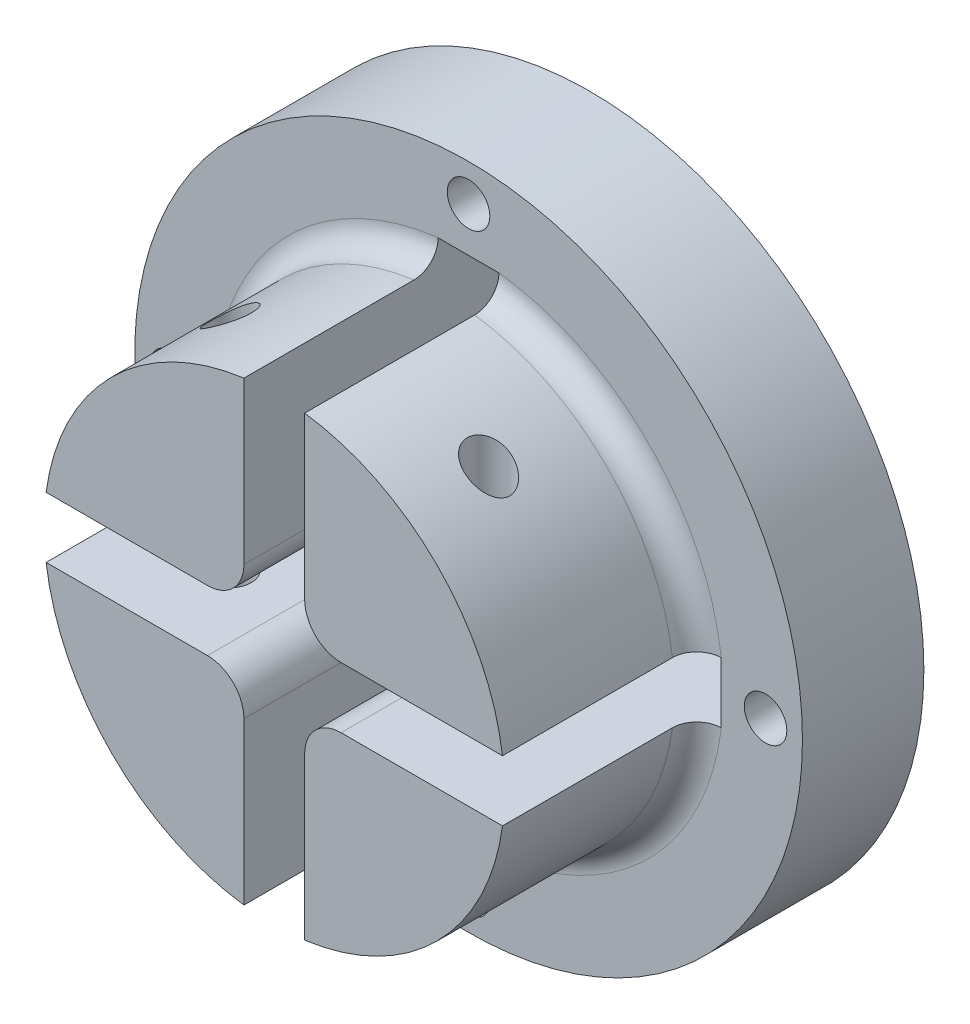
SolidWorks part; units mm, degrees
ref_plane "前视基准面" through (0, 0, 0) normal (0, 0, 1) x (1, 0, 0)
ref_plane "上视基准面" through (0, 0, 0) normal (0, 1, 0) x (1, 0, 0)
ref_plane "右视基准面" through (0, 0, 0) normal (1, 0, 0) x (0, 0, -1)
sketch "草图1" plane through (0, 0, 0) normal (0, 0, 1) x (1, 0, 0)
  circle A0 centre (0, 0) radius 27.5
  dimension "D1" = 55
extrude "凸台-拉伸1" add sketch "草图1" along normal blind 10
sketch "草图2" plane through (0, 0, 10) normal (0, 0, 1) x (1, 0, 0)
  line L0 (-2.5, 5.5) -> (-2.5, 17.5)
  line L1 (17.5, -2.5) -> (5.5, -2.5)
  line L3 (17.5, 2.5) -> (5.5, 2.5)
  line L5 (0, 2.5) -> (0, -2.5) construction
  line L6 (17.5, 0) -> (-17.5, 0) construction
  line L8 (2.5, -17.5) -> (2.5, -5.5)
  line L10 (-2.5, -17.5) -> (-2.5, -5.5)
  line L11 (0, 17.5) -> (0, -17.5) construction
  line L12 (2.5, 0) -> (-2.5, 0) construction
  line L13 (-5.5, -2.5) -> (-17.5, -2.5)
  line L14 (-5.5, 2.5) -> (-17.5, 2.5)
  line L15 (2.5, 5.5) -> (2.5, 17.5)
  line L16 (-17.5, 2.5) -> (-18.793, 2.5)
  line L17 (-17.5, -2.5) -> (-18.793, -2.5)
  line L18 (-2.5, 17.5) -> (-2.5, 18.793)
  line L19 (2.5, 17.5) -> (2.5, 18.793)
  line L20 (17.5, 2.5) -> (18.793, 2.5)
  line L21 (17.5, -2.5) -> (18.793, -2.5)
  line L22 (-2.5, -17.5) -> (-2.5, -18.793)
  line L23 (2.5, -17.5) -> (2.5, -18.793)
  arc A0 (5.5, -2.5) -> (2.5, -5.5) centre (5.5, -5.5) ccw
  arc A1 (-2.5, -5.5) -> (-5.5, -2.5) centre (-5.5, -5.5) ccw
  arc A2 (5.5, 2.5) -> (2.5, 5.5) centre (5.5, 5.5) cw
  arc A3 (-2.5, 5.5) -> (-5.5, 2.5) centre (-5.5, 5.5) cw
  circle A4 centre (0, 0) radius 27.5 construction
  circle A5 centre (0, 0) radius 27.5 construction
  arc A6 (-18.793, -2.5) -> (-2.5, -18.793) centre (0, 0) ccw
  arc A7 (-2.5, 18.793) -> (-18.793, 2.5) centre (0, 0) ccw
  arc A8 (18.793, 2.5) -> (2.5, 18.793) centre (0, 0) ccw
  arc A9 (2.5, -18.793) -> (18.793, -2.5) centre (0, 0) ccw
  point P0 (0, 0)
  point P4 (0, 0)
  point P22 (-2.5, -2.5)
  point P25 (2.5, 2.5)
  point P28 (-2.5, 2.5)
  dimension "D5" = 3
  dimension "D1" = 5
  dimension "D2" = 5
  dimension "D3" = 35
  dimension "D4" = 35
extrude "凸台-拉伸2" add sketch "草图2" along normal blind 16
sketch "草图6" plane through (0, 0, 10) normal (0, 0, 1) x (1, 0, 0)
  line L0 (18.793, -2.5) -> (5.5, -2.5) construction
  line L1 (5.5, 2.5) -> (18.793, 2.5) construction
  line L2 (2.5, -5.5) -> (2.5, -18.793) construction
  line L3 (-2.5, -18.793) -> (-2.5, -5.5) construction
  line L4 (-5.5, -2.5) -> (-18.793, -2.5) construction
  line L5 (-18.793, 2.5) -> (-5.5, 2.5) construction
  line L6 (2.5, 18.793) -> (2.5, 5.5) construction
  line L7 (-2.5, 5.5) -> (-2.5, 18.793) construction
  line L8 (18.793, -2.5) -> (5.5, -2.5)
  line L9 (5.5, 2.5) -> (18.793, 2.5)
  line L10 (2.5, -5.5) -> (2.5, -18.793)
  line L11 (-2.5, -18.793) -> (-2.5, -5.5)
  line L12 (-5.5, -2.5) -> (-18.793, -2.5)
  line L13 (-18.793, 2.5) -> (-5.5, 2.5)
  line L14 (2.5, 18.793) -> (2.5, 5.5)
  line L15 (-2.5, 5.5) -> (-2.5, 18.793)
  line L16 (-2.5, 5.5) -> (-2.5, 2.5)
  line L17 (-2.5, 2.5) -> (-5.5, 2.5)
  line L18 (-5.5, -2.5) -> (-2.5, -2.5)
  line L19 (-2.5, -2.5) -> (-2.5, -5.5)
  line L20 (2.5, 5.5) -> (2.5, 2.5)
  line L21 (2.5, 2.5) -> (5.5, 2.5)
  line L22 (5.5, -2.5) -> (2.5, -2.5)
  line L23 (2.5, -2.5) -> (2.5, -5.5)
  line L24 (-18.793, 2.5) -> (-18.793, -2.5)
  line L26 (-2.5, 18.793) -> (2.5, 18.793)
  line L27 (18.793, 2.5) -> (18.793, -2.5)
  line L28 (2.5, -18.793) -> (-2.5, -18.793)
extrude "切除-拉伸3" cut sketch "草图6" against normal blind 20
fillet "圆角3" radius 2 4 edges at (-13.4057, 13.4057, 10) (13.4057, 13.4057, 10) (13.4057, -13.4057, 10) (-13.4057, -13.4057, 10)
sketch "草图7" plane through (0, 0, 0) normal (0, 0, -1) x (-1, 0, 0)
  line L0 (18.793, 2.5) -> (18.793, -2.5) construction
  line L1 (2.5, -18.793) -> (-2.5, -18.793) construction
  line L2 (-18.793, -2.5) -> (-18.793, 2.5) construction
  line L3 (-2.5, 18.793) -> (2.5, 18.793) construction
  line L4 (18.793, 2.5) -> (18.793, -2.5)
  line L5 (2.5, -18.793) -> (-2.5, -18.793)
  line L6 (-18.793, -2.5) -> (-18.793, 2.5)
  line L7 (-2.5, 18.793) -> (2.5, 18.793)
  line L8 (-18.793, 2.5) -> (-20.793, 2.5)
  line L9 (-20.793, 2.5) -> (-20.793, -2.5)
  line L10 (-20.793, -2.5) -> (-18.793, -2.5)
  line L11 (-2.5, 18.793) -> (-2.5, 20.793)
  line L12 (-2.5, 20.793) -> (2.5, 20.793)
  line L13 (2.5, 20.793) -> (2.5, 18.793)
  line L14 (18.793, 2.5) -> (20.793, 2.5)
  line L15 (20.793, 2.5) -> (20.793, -2.5)
  line L16 (20.793, -2.5) -> (18.793, -2.5)
  line L17 (-2.5, -18.793) -> (-2.5, -20.793)
  line L18 (-2.5, -20.793) -> (2.5, -20.793)
  line L19 (2.5, -20.793) -> (2.5, -18.793)
  dimension "D1" = 2
  dimension "D2" = 2
  dimension "D3" = 2
  dimension "D4" = 2
extrude "切除-拉伸4" cut sketch "草图7" against normal blind 20
sketch "草图8" plane through (0, 0, 10) normal (0, 0, 1) x (1, 0, 0)
  circle A0 centre (0, 24.4602) radius 1.75
  circle A1 centre (24.4602, 0) radius 1.75
  circle A2 centre (0, -24.4602) radius 1.75
  circle A3 centre (-24.4602, 0) radius 1.75
  point P11 (0, 0)
  dimension "D1" = 3.5
  dimension "D2" = 4
extrude "切除-拉伸5" cut sketch "草图8" against normal blind 20
sketch "草图9" plane through (0, 0, 0) normal (0, 1, 0) x (1, 0, 0)
  line L0 (-18.793, -19) -> (18.793, -19) construction
  line L1 (-18.793, -26) -> (-18.793, -12) construction
  line L2 (18.793, -26) -> (18.793, -12) construction
  line L3 (-10.6465, -26) -> (-10.6465, -12) construction
  line L4 (-18.793, -26) -> (-2.5, -26) construction
  line L5 (-2.5, -12) -> (-18.793, -12) construction
  line L6 (0, -10) -> (0, -38) construction
  line L7 (-27.5, -10) -> (27.5, -10) construction
  circle A0 centre (-10.6465, -19) radius 1.75
  circle A1 centre (10.6465, -19) radius 1.75
  dimension "D1" = 3.5
extrude "切除-拉伸6" cut sketch "草图9" against normal mid plane 61
